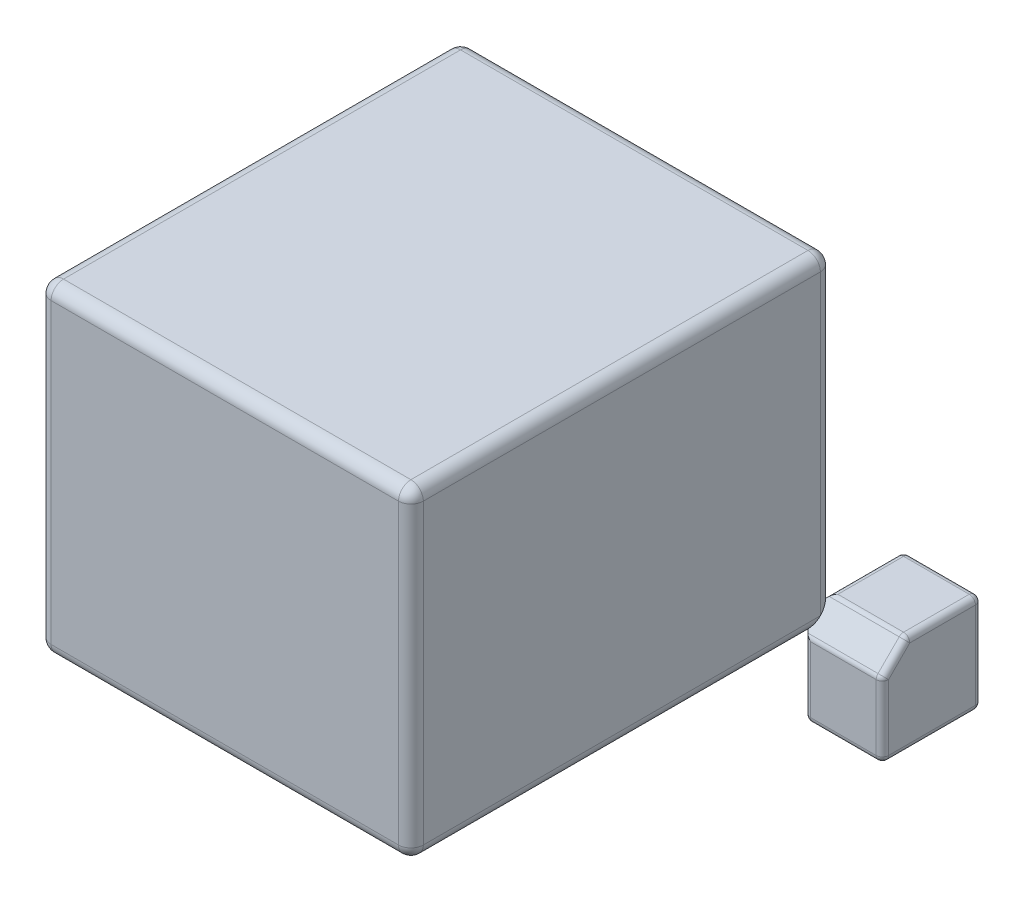
SolidWorks part; units mm, degrees
ref_plane "Front Plane" through (0, 0, 0) normal (0, 0, 1) x (1, 0, 0)
ref_plane "Top Plane" through (0, 0, 0) normal (0, 1, 0) x (1, 0, 0)
ref_plane "Right Plane" through (0, 0, 0) normal (1, 0, 0) x (0, 0, -1)
sketch "Sketch1" plane through (0, 0, 0) normal (0, 0, 1) x (1, 0, 0)
  line L1 (0, 0) -> (30, 0)
  line L2 (0, 0) -> (0, 26)
  line L3 (0, 26) -> (30, 26)
  line L4 (30, 0) -> (30, 26)
  dimension "D1" = 30
  dimension "D2" = 26
extrude "Boss-Extrude1" add sketch "Sketch1" along normal blind 34
sketch "Sketch2" plane through (0, 0, 0) normal (0, 0, -1) x (-1, 0, 0)
  line L0 (-30, 0) -> (-30, 26) construction
  line L1 (-28, 2) -> (-36, 2)
  line L2 (-28, 2) -> (-28, -6)
  line L3 (-28, -6) -> (-36, -6)
  line L4 (-36, 2) -> (-36, -6)
  line L5 (0, 0) -> (-30, 0) construction
  dimension "D1" = 2
  dimension "D2" = 2
  dimension "D3" = 8
  dimension "D4" = 8
shell "Shell1" thickness 1
extrude "Boss-Extrude3" add sketch "Sketch2" along normal blind 6 and the other way blind 2 contours L3 L4 L1 L2
chamfer "Chamfer2" distance 2 angle 45 3 edges at (33, 2, 2) (28, 2, -3) (28, -3, 2)
fillet "Fillet1" radius 1 12 edges at (0, 13, 0) (14, 0, 0) (30, 14, 0) (15, 26, 0) (15, 0, 34) (30, 13, 34) (15, 26, 34) (0, 26, 17) (30, 26, 17) (30, 0, 18) (0, 0, 17) (0, 13, 34)
fillet "Fillet2" radius 0.5 18 edges at (36, -6, -2) (32, -6, -6) (29, -6, 1) (33, -6, 2) (28, -6, -3) (28, -3, -6) (28, 0, -3) (28, -3, 0) (33, 0, 2) (29, 1, -6) (33, 2, -6) (36, 2, -3) (33, 2, 0) (30, 2, -3) (36, -3, 2) (36, -2, -6) (30, -3, 2) (36, 1, 1)
